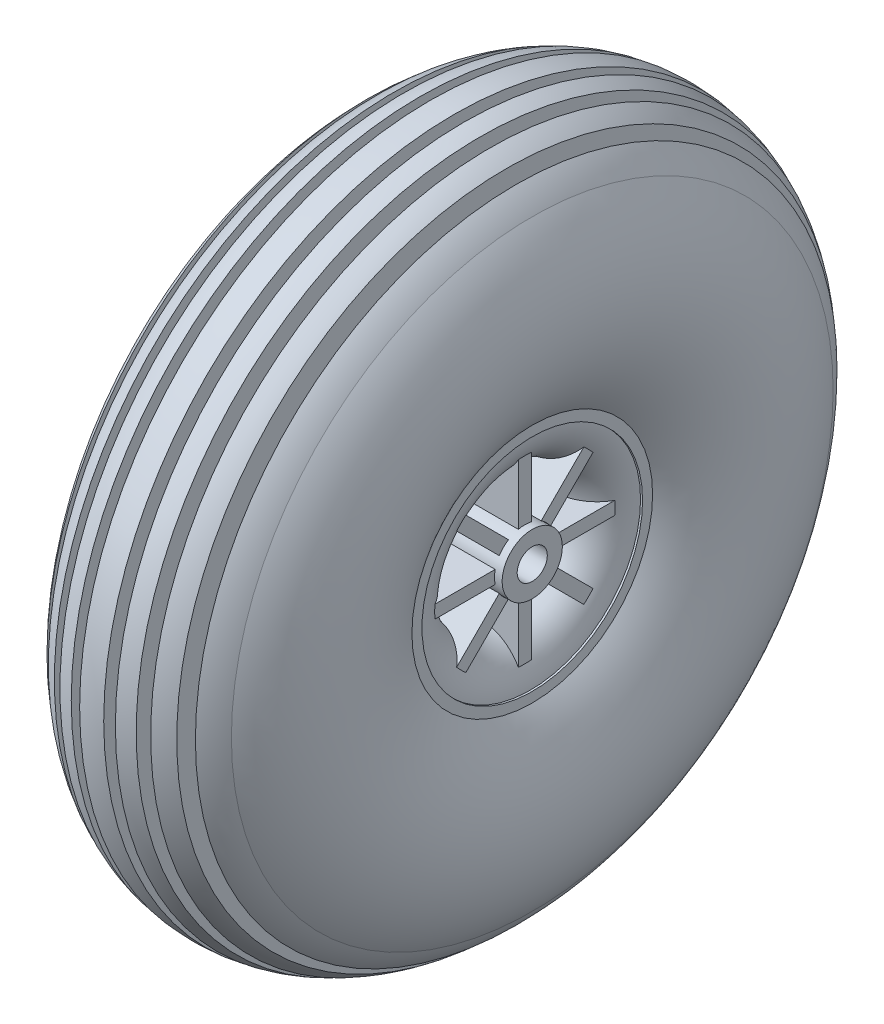
SolidWorks part; units mm, degrees
material "Rubber"
ref_plane "Front Plane" through (0, 0, 0) normal (0, 0, 1) x (1, 0, 0)
ref_plane "Top Plane" through (0, 0, 0) normal (0, 1, 0) x (1, 0, 0)
ref_plane "Right Plane" through (0, 0, 0) normal (1, 0, 0) x (0, 0, -1)
sketch "Sketch1" plane through (0, 0, 0) normal (0, 0, 1) x (1, 0, 0)
  line L0 (0, 0) -> (-50000, 0) construction
  line L1 (-11.43, 15.24) -> (11.43, 15.24)
  line L2 (0, 0) -> (0, 50000) construction
  line L3 (-11.43, 38.1) -> (11.43, 38.1)
  line L4 (-44.9633, 26.67) -> (49955.0367, 26.67) construction
  line L5 (-10.0122, 39.987) -> (8.128, 39.987) construction
  line L6 (-8.128, 41.6523) -> (8.2157, 41.6523) construction
  line L7 (-9.398, 40.6266) -> (-9.398, 38.1)
  line L8 (-8.128, 41.7193) -> (-8.128, 38.1)
  line L9 (-8.128, 38.1) -> (-9.398, 38.1)
  line L10 (-6.096, 42.9907) -> (-6.096, 39.987)
  line L11 (-6.096, 39.987) -> (-4.826, 39.987)
  line L12 (-4.826, 39.987) -> (-4.826, 43.5552)
  line L13 (-2.794, 44.1569) -> (-2.794, 41.6523)
  line L14 (-2.794, 41.6523) -> (-1.524, 41.6523)
  line L15 (-1.524, 41.6523) -> (-1.524, 44.3635)
  line L16 (9.398, 40.6266) -> (9.398, 38.1)
  line L17 (8.128, 41.7193) -> (8.128, 39.987)
  line L18 (6.096, 42.9907) -> (6.096, 39.987)
  line L19 (8.128, 39.987) -> (8.128, 38.1)
  line L20 (8.128, 38.1) -> (9.398, 38.1)
  line L21 (9.398, 39.987) -> (10.0122, 39.987) construction
  line L22 (6.096, 39.987) -> (4.826, 39.987)
  line L23 (4.826, 39.987) -> (4.826, 43.5552)
  line L24 (2.794, 44.1569) -> (2.794, 41.6523)
  line L25 (2.794, 41.6523) -> (1.524, 41.6523)
  line L26 (1.524, 41.6523) -> (1.524, 44.3635)
  line L27 (-11.43, 15.24) -> (-11.43, 13.97)
  line L28 (-11.43, 13.97) -> (-11.176, 13.97)
  line L29 (-11.43, 1.905) -> (11.43, 1.905)
  line L30 (-5.5887, 8.509) -> (5.5887, 8.509)
  line L31 (-11.43, 3.81) -> (11.43, 3.81)
  line L32 (11.176, 13.97) -> (11.43, 13.97)
  line L33 (11.43, 13.97) -> (11.43, 15.24)
  line L34 (11.43, 3.81) -> (11.43, 1.905)
  line L35 (-11.43, 3.81) -> (-11.43, 1.905)
  line L36 (-0.635, 8.509) -> (-0.635, 3.81)
  line L37 (-0.635, 3.81) -> (0.635, 3.81)
  line L38 (0.635, 3.81) -> (0.635, 8.509)
  arc A0 (-11.43, 38.1) -> (-11.43, 15.24) centre (3.81, 26.67) ccw
  arc A1 (11.43, 15.24) -> (11.43, 38.1) centre (-3.81, 26.67) ccw
  arc A2 (11.43, 38.1) -> (9.398, 40.6266) centre (0, 30.988) ccw
  arc A3 (-9.398, 40.6266) -> (-11.43, 38.1) centre (0, 30.988) ccw
  arc A4 (-6.096, 42.9907) -> (-8.128, 41.7193) centre (0, 30.988) ccw
  arc A5 (-2.794, 44.1569) -> (-4.826, 43.5552) centre (0, 30.988) ccw
  arc A6 (1.524, 44.3635) -> (-1.524, 44.3635) centre (0, 30.988) ccw
  arc A7 (4.826, 43.5552) -> (2.794, 44.1569) centre (0, 30.988) ccw
  arc A8 (8.128, 41.7193) -> (6.096, 42.9907) centre (0, 30.988) ccw
  arc A9 (-11.176, 13.97) -> (-5.5887, 8.509) centre (-5.5887, 14.0977) ccw
  arc A12 (5.5887, 8.509) -> (11.176, 13.97) centre (5.5887, 14.0977) ccw
  point P11 (-15.24, 26.67)
  point P12 (15.24, 26.67)
  point P13 (0, 44.45)
  dimension "D1" = 22.86
  dimension "D2" = 11.43
  dimension "D3" = 15.24
  dimension "D4" = 22.86
  dimension "D5" = 11.43
  dimension "D6" = 38.1
  dimension "D7" = 26.67
  dimension "D8" = 15.24
  dimension "D9" = 15.24
  dimension "D10" = 44.45
  dimension "D11" = 1.27
  dimension "D12" = 2.032
  dimension "D13" = 1.27
  dimension "D14" = 2.032
  dimension "D15" = 1.27
  dimension "D16" = 2.032
  dimension "D17" = 2.032
  dimension "D18" = 1.27
  dimension "D19" = 2.032
  dimension "D20" = 1.27
  dimension "D21" = 1.27
  dimension "D22" = 2.032
  dimension "D23" = 1.27
  dimension "D24" = 0.254
  dimension "D26" = 8.509
  dimension "D25" = 1.905
  dimension "D27" = 3.81
  dimension "D28" = 1.27
  dimension "D29" = 0.635
revolve "Revolve1" add sketch "Sketch1" angle 360 about L0 region at (0, 26.67, 0) region at (-10.1035, 38.9762, 0) region at (10.1035, 38.9762, 0) region at (0, 40.6292, 0)
revolve "Revolve2" add sketch "Sketch1<3>" angle 360 about L0 region at (0, 12.0933, 0)
sketch "Sketch1<3>" plane through (0, 0, 0) normal (0, 0, 1) x (1, 0, 0) same geometry as "Sketch1"
revolve "Revolve3" add sketch "Sketch1<4>" angle 360 about L0
sketch "Sketch1<4>" plane through (0, 0, 0) normal (0, 0, 1) x (1, 0, 0) same geometry as "Sketch1"
revolve "Revolve5" add sketch "Sketch1<5>" angle 360 about L0 region at (0, 6.1595, 0)
sketch "Sketch1<5>" plane through (0, 0, 0) normal (0, 0, 1) x (1, 0, 0) same geometry as "Sketch1"
sketch "Sketch4" plane through (0.635, 0, 0) normal (1, 0, 0) x (0, 0, -1)
  line L0 (-0.8255, 11.4002) -> (-0.8255, 3.7505)
  line L1 (0.8255, 11.4002) -> (0.8255, 3.7505)
  line L2 (0, -1007.6805) -> (0, -11.43) construction
  line L3 (7.4774, 8.6448) -> (2.0683, 3.2357)
  line L4 (8.6448, 7.4774) -> (3.2357, 2.0683)
  line L5 (11.4002, 0.8255) -> (3.7505, 0.8255)
  line L6 (11.4002, -0.8255) -> (3.7505, -0.8255)
  line L7 (8.6448, -7.4774) -> (3.2357, -2.0683)
  line L8 (7.4774, -8.6448) -> (2.0683, -3.2357)
  line L9 (0.8255, -11.4002) -> (0.8255, -3.7505)
  line L10 (-0.8255, -11.4002) -> (-0.8255, -3.7505)
  line L11 (0, 3.8402) -> (0, 50000) construction
  line L12 (-7.4774, -8.6448) -> (-2.0683, -3.2357)
  line L13 (-8.6448, -7.4774) -> (-3.2357, -2.0683)
  line L14 (-11.4002, -0.8255) -> (-3.7505, -0.8255)
  line L15 (-11.4002, 0.8255) -> (-3.7505, 0.8255)
  line L16 (-8.6448, 7.4774) -> (-3.2357, 2.0683)
  line L17 (-7.4774, 8.6448) -> (-2.0683, 3.2357)
  arc A0 (-0.8255, 11.4002) -> (0.8255, 11.4002) centre (0, 0) cw
  circle A1 centre (0, 0) radius 11.43 construction
  arc A2 (-0.8255, 3.7505) -> (0.8255, 3.7505) centre (0, 0) cw
  arc A3 (2.0683, 3.2357) -> (3.2357, 2.0683) centre (0, 0) cw
  arc A5 (7.4774, 8.6448) -> (8.6448, 7.4774) centre (0, 0) cw
  arc A6 (3.7505, 0.8255) -> (3.7505, -0.8255) centre (0, 0) cw
  arc A7 (11.4002, 0.8255) -> (11.4002, -0.8255) centre (0, 0) cw
  arc A8 (3.2357, -2.0683) -> (2.0683, -3.2357) centre (0, 0) cw
  arc A9 (8.6448, -7.4774) -> (7.4774, -8.6448) centre (0, 0) cw
  arc A10 (0.8255, -3.7505) -> (-0.8255, -3.7505) centre (0, 0) cw
  arc A11 (0.8255, -11.4002) -> (-0.8255, -11.4002) centre (0, 0) cw
  arc A12 (-2.0683, -3.2357) -> (-3.2357, -2.0683) centre (0, 0) cw
  arc A13 (0.8255, 3.7505) -> (-2.0683, 3.2357) centre (0, 0) ccw construction
  arc A14 (-7.4774, -8.6448) -> (-8.6448, -7.4774) centre (0, 0) cw
  arc A15 (-3.7505, -0.8255) -> (-3.7505, 0.8255) centre (0, 0) cw
  arc A16 (-11.4002, -0.8255) -> (-11.4002, 0.8255) centre (0, 0) cw
  arc A17 (-3.2357, 2.0683) -> (-2.0683, 3.2357) centre (0, 0) cw
  arc A18 (-8.6448, 7.4774) -> (-7.4774, 8.6448) centre (0, 0) cw
  point P43 (0, 0)
  point P53 (0, 0)
  dimension "D1" = 1.651
  dimension "D2" = 1.651
  dimension "D3" = 0.8255
  dimension "D4" = 8
extrude "Boss-Extrude1" add sketch "Sketch4" along normal blind 9.8552
extrude "Boss-Extrude2" add sketch "Sketch4<2>" against normal blind 11.1252
sketch "Sketch4<2>" plane through (0.635, 0, 0) normal (1, 0, 0) x (0, 0, -1) same geometry as "Sketch4"
equation "\"D2@Sketch1\"=.5*\"D1@Sketch1\""
equation "\"D4@Sketch1\"=\"D1@Sketch1\""
equation "\"D5@Sketch1\"=.5*\"D1@Sketch1\""
equation "\"D7@Sketch1\"=(\"D3@Sketch1\"+\"D6@Sketch1\")/2"
equation "\"D8@Sketch1\"=.6"
equation "\"D14@Sketch1\"=\"D12@Sketch1\""
equation "\"D16@Sketch1\"=\"D12@Sketch1\""
equation "\"D19@Sketch1\"=\"D17@Sketch1\""
equation "\"D20@Sketch1\"=\"D18@Sketch1\""
